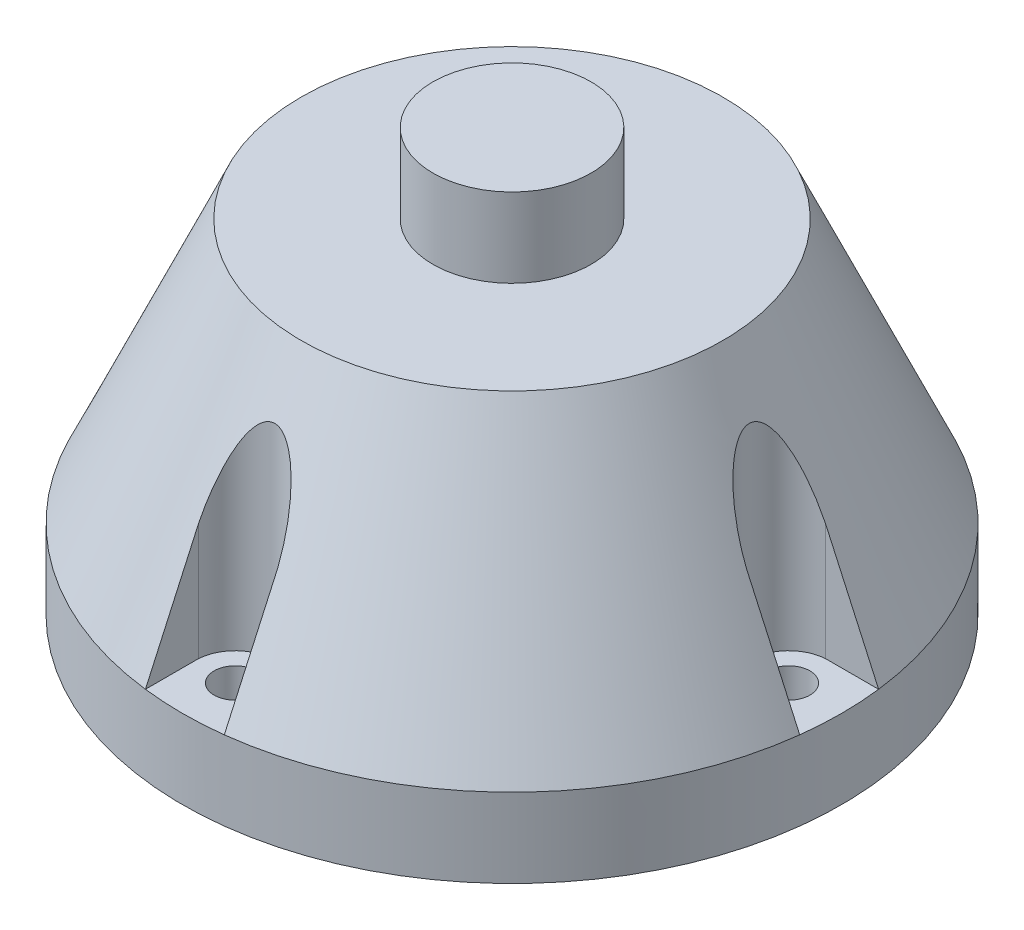
SolidWorks part; units mm, degrees
material "1060 Alloy"
ref_plane "Front Plane" through (0, 0, 0) normal (0, 0, 1) x (1, 0, 0)
ref_plane "Top Plane" through (0, 0, 0) normal (0, 1, 0) x (1, 0, 0)
ref_plane "Right Plane" through (0, 0, 0) normal (1, 0, 0) x (0, 0, -1)
sketch "Sketch3" plane through (0, 0, 0) normal (0, 0, 1) x (1, 0, 0)
  line L0 (0, 15) -> (62.5, 15)
  line L1 (62.5, 15) -> (40, 65)
  line L2 (40, 65) -> (15, 65)
  line L3 (0, 65) -> (0, 15)
  line L6 (0, 65) -> (0, 80)
  line L7 (0, 80) -> (15, 80)
  line L8 (15, 65) -> (15, 80)
  dimension "D1" = 65
  dimension "D2" = 62.5
  dimension "D3" = 40
  dimension "D4" = 15
  dimension "D5" = 15
  dimension "D6" = 15
revolve "Revolve1" add sketch "Sketch3" angle 360 about L3
sketch "Sketch4" plane through (0, 15, 0) normal (0, -1, 0) x (1, 0, 0)
  line L0 (7.4808, -51.9643) -> (7.4808, -62.0507)
  line L1 (51.9643, 7.4808) -> (62.0507, 7.4808)
  line L3 (51.9643, -7.4808) -> (62.0507, -7.4808)
  line L4 (-7.4808, -51.9643) -> (-7.4808, -62.0507)
  line L5 (-51.9643, -7.4808) -> (-62.0507, -7.4808)
  line L6 (-51.9643, 7.4808) -> (-62.0507, 7.4808)
  line L7 (-7.4808, 51.9643) -> (-7.4808, 62.0507)
  line L8 (7.4808, 51.9643) -> (7.4808, 62.0507)
  circle A1 centre (0, 0) radius 62.5 construction
  arc A2 (51.9643, 7.4808) -> (7.4808, 51.9643) centre (0, 0) ccw construction
  arc A3 (51.9643, 7.4808) -> (51.9643, -7.4808) centre (52.5, 0) ccw
  arc A4 (7.4808, -51.9643) -> (-7.4808, -51.9643) centre (0, -52.5) ccw
  arc A5 (-51.9643, -7.4808) -> (-51.9643, 7.4808) centre (-52.5, 0) ccw
  arc A6 (-7.4808, 51.9643) -> (7.4808, 51.9643) centre (0, 52.5) ccw
  circle A7 centre (0, 0) radius 62.5
  arc A8 (-7.4808, 51.9643) -> (-51.9643, 7.4808) centre (0, 0) ccw construction
  circle A9 centre (52.5, 0) radius 4
  arc A10 (-51.9643, -7.4808) -> (-7.4808, -51.9643) centre (0, 0) ccw construction
  circle A11 centre (0, -52.5) radius 4
  arc A12 (7.4808, -51.9643) -> (51.9643, -7.4808) centre (0, 0) ccw construction
  circle A13 centre (-52.5, 0) radius 4
  circle A14 centre (0, 52.5) radius 4
  point P27 (0, 0)
  point P36 (0, 0)
  circle M2 centre (0, 0) radius 62.5
  dimension "D1" = 105
  dimension "D2" = 15
  dimension "D4" = 8
  dimension "D3" = 4
  dimension "D5" = 4
extrude "Boss-Extrude2" add sketch "Sketch4" along normal blind 15 contours A6 L7 L6 A5 L5 L4 A4 L0 L3 A3 L1 L8 M2 | L5 A5 L6 M2 | L7 A6 L8 M2 | L1 A3 L3 M2 | L0 A4 L4 M2 region at (0, 15, 0) region at (7.2506, 15, -57.0075) region at (57.0075, 15, -7.2506) region at (-62.2698, 15, 0) region at (0, 15, 62.2698)
extrude "Cut-Extrude1" cut sketch "Sketch4<5>" against normal up to surface contours L7 A6 L8 A14 M2 | L1 A3 L3 A9 M2 | L0 A4 L4 A11 M2 | L5 A5 L6 A13 M2 | A14 | A11 | A13 | A9 region at (7.2506, 15, -57.0075) region at (57.0075, 15, -7.2506) region at (-62.2698, 15, 0) region at (0, 15, 62.2698) region at (0, 15, 52.5) up to face at (-40, 65, 0)
sketch "Sketch4<5>" plane through (0, 15, 0) normal (0, -1, 0) x (1, 0, 0) same geometry as "Sketch4"
sketch "Sketch5" plane through (0, 0, 0) normal (0, -1, 0) x (1, 0, 0)
  circle A0 centre (0, 0) radius 15 construction
  point P0 (0, 0)
